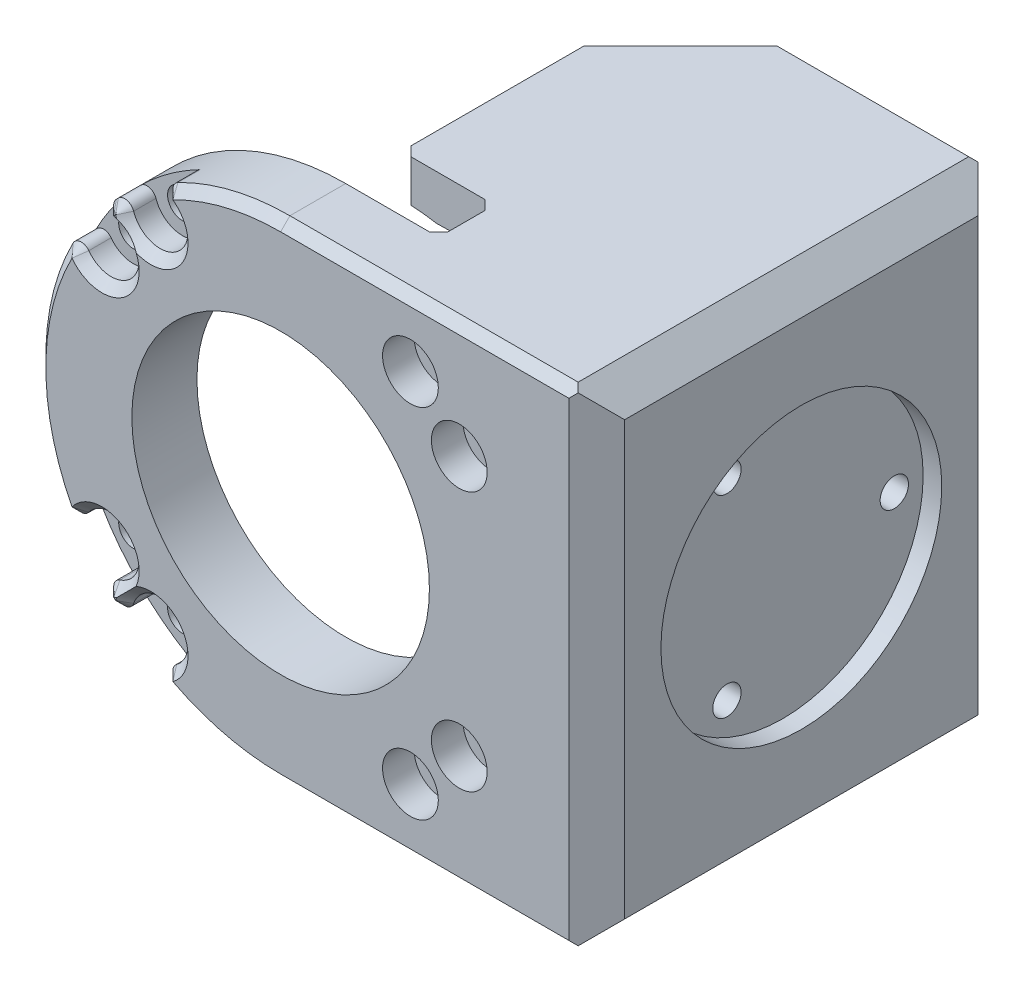
SolidWorks part; units mm, degrees
other "标注1"
sketch "草图23" plane through (38, 52.5005, -37) normal (0.8245, 0.2959, -0.4823) x (-0.5412, 0.1636, -0.8248)
material "ABS"
ref_plane "前视基准面" through (0, 0, 0) normal (0, 0, 1) x (1, 0, 0)
ref_plane "上视基准面" through (0, 0, 0) normal (0, 1, 0) x (1, 0, 0)
ref_plane "右视基准面" through (0, 0, 0) normal (1, 0, 0) x (0, 0, -1)
other "Configuration Table"
sketch "草图1" plane through (0, 0, 0) normal (0, 0, 1) x (1, 0, 0)
  line L2 (0, 0) -> (0, 52.5) construction
  line L6 (-26.25, 26.25) -> (30, 26.25) construction
  line L7 (0, 26.25) -> (-13.9599, 7.0358) construction
  line L8 (0, 26.25) -> (-19.2142, 12.2901) construction
  line L23 (0, 0) -> (30, 0)
  line L24 (0, 0) -> (0, 52.5) construction
  line L25 (0, 52.5) -> (30, 52.5)
  line L26 (30, 0) -> (30, 52.5)
  circle A2 centre (0, 26.25) radius 16
  circle A4 centre (0, 26.25) radius 23.75 construction
  arc A25 (0, 52.5) -> (0, 0) centre (0, 26.25) ccw
  dimension "D3" = 32
  dimension "D6" = 47.5
  dimension "D1" = 52.5
  dimension "D2" = 30
  dimension "D9" = 36
  dimension "D10" = 36
extrude "凸台-拉伸1" add sketch "草图1" along normal blind 7
sketch "草图2" plane through (30, 0, 0) normal (1, 0, 0) x (0, 0, -1)
  line L0 (-7, 52.5) -> (0, 52.5) construction
  line L1 (-7, 0) -> (37, 0)
  line L2 (-7, 0) -> (-7, 52.5)
  line L3 (-7, 52.5) -> (37, 52.5)
  line L4 (37, 0) -> (37, 52.5)
  dimension "D1" = 44
extrude "凸台-拉伸2" add sketch "草图2" along normal blind 4
chamfer "倒角1" distance 3 angle 45 2 edges at (34, 26.25, -37) (34, 26.25, 7)
sketch "草图6" plane through (34, 0, 0) normal (1, 0, 0) x (0, 0, -1)
  line L0 (-4, 0) -> (34, 0) construction
  line L3 (-7, 0) -> (-7, 52.5) construction
  circle A1 centre (15, 26.25) radius 12 construction
  circle A2 centre (27, 26.25) radius 1.525
  circle A3 centre (9, 15.8577) radius 1.525
  circle A4 centre (9, 36.6423) radius 1.525
  dimension "D4" = 24
  dimension "D5" = 3.05
  dimension "D1" = 26.25
  dimension "D2" = 22
  dimension "D6" = 3
sketch "草图16" plane through (0, 0, 0) normal (0, 0, -1) x (-1, 0, 0)
  line L2 (-30, 52.5) -> (0, 52.5)
  line L3 (0, 52.5) -> (0, 48)
  line L4 (-30, 0) -> (0, 0)
  line L5 (-30, 52.5) -> (-30, 0)
  line L6 (-21.4196, 30.0268) -> (0, 26.25) construction
  line L7 (0, 26.25) -> (-21.4196, 22.4732) construction
  line L8 (0, 26.25) -> (-30, 26.25) construction
  line L9 (0, 26.25) -> (0, 52.5) construction
  line L10 (0, 26.25) -> (0, 0) construction
  line L11 (0, 26.25) -> (-3.7768, 47.6696) construction
  line L12 (0, 26.25) -> (-3.7768, 4.8304) construction
  line L13 (0, 4.5) -> (0, 0)
  line L14 (-13.2899, 47.8727) -> (-3.7768, 47.6696)
  line L16 (-21.6834, 39.8188) -> (-21.4196, 30.0268)
  line L18 (-21.4196, 22.4732) -> (-21.6227, 12.9601)
  line L19 (-13.5688, 4.5666) -> (-3.7768, 4.8304)
  line L20 (-13.9599, 45.4642) -> (0, 26.25) construction
  line L21 (0, 26.25) -> (-13.9599, 7.0358) construction
  line L22 (-19.2142, 40.2099) -> (0, 26.25) construction
  line L23 (-19.2142, 12.2901) -> (0, 26.25) construction
  circle A0 centre (0, 26.25) radius 26.25 construction
  circle A1 centre (0, 26.25) radius 21.75 construction
  circle A2 centre (0, 26.25) radius 16 construction
  circle A3 centre (-13.9599, 45.4642) radius 2.5 construction
  circle A4 centre (-19.2142, 40.2099) radius 2.5 construction
  circle A5 centre (-19.2142, 12.2901) radius 2.5 construction
  circle A6 centre (-13.9599, 7.0358) radius 2.5 construction
  arc A8 (-21.4196, 30.0268) -> (-21.4196, 22.4732) centre (0, 26.25) ccw
  arc A11 (-15.4294, 47.4867) -> (-21.2367, 41.6794) centre (0, 26.25) ccw
  arc A12 (-3.7768, 47.6696) -> (0, 48) centre (0, 26.25) cw
  arc A13 (-3.7768, 4.8304) -> (0, 4.5) centre (0, 26.25) ccw
  arc A14 (-21.2367, 10.8206) -> (-15.4294, 5.0133) centre (0, 26.25) ccw
  arc A15 (-15.4294, 47.4867) -> (-13.2899, 47.8727) centre (-13.9599, 45.4642) cw
  arc A16 (-21.2367, 41.6794) -> (-21.6834, 39.8188) centre (-19.2142, 40.2099) ccw
  arc A17 (-21.2367, 10.8206) -> (-21.6227, 12.9601) centre (-19.2142, 12.2901) cw
  arc A18 (-15.4294, 5.0133) -> (-13.5688, 4.5666) centre (-13.9599, 7.0358) ccw
  circle A19 centre (0, 26.25) radius 23.75 construction
  point P9 (0, 0)
  dimension "D1" = 52.5
  dimension "D2" = 43.5
  dimension "D5" = 10
  dimension "D3" = 10
  dimension "D8" = 47.5
  dimension "D12" = 5
  dimension "D13" = 5
  dimension "D4" = 10
  dimension "D6" = 10
  dimension "D7" = 36
  dimension "D9" = 36
  dimension "D10" = 36
  dimension "D11" = 36
extrude "凸台-拉伸5" add sketch "草图16" along normal blind 37
chamfer "倒角7" distance 10 angle 45 2 edges at (0, 2.25, -37) (0, 50.25, -37)
chamfer "倒角8" distance 3 angle 45 2 edges at (34, 0, -15) (34, 52.5, -15)
chamfer "倒角9" distance 1 angle 45 5 edges at (5, 52.5, -32) (20.5, 52.5, -37) (20.5, 0, -37) (5, 0, -32) (0, 0, -13.5)
sketch "草图18" plane through (0, 0, 7) normal (0, 0, 1) x (1, 0, 0)
  line L0 (0, 26.25) -> (0, 2.5) construction
  line L1 (0, 26.25) -> (-23.75, 26.25) construction
  line L2 (0, 26.25) -> (-19.2142, 12.2901) construction
  line L3 (0, 26.25) -> (-13.9599, 7.0358) construction
  circle A0 centre (0, 26.25) radius 23.75 construction
  point P3 (-19.2142, 12.2901)
  point P6 (-13.9599, 7.0358)
  point P12 (-13.9599, 45.4642)
  point P13 (-19.2142, 40.2099)
  point P14 (19.2142, 40.2099)
  point P15 (13.9599, 45.4642)
  point P16 (13.9599, 7.0358)
  point P17 (19.2142, 12.2901)
  dimension "D1" = 47.5
  dimension "D2" = 36
  dimension "D3" = 36
  dimension "D4" = 4
hole_wizard "M3 六角圆柱头螺钉的柱形沉头孔1" positions "草图18" profile "草图19" counterbore size "M3" standard "GB" end condition through all
sketch "草图19" plane through (19.2142, 12.2901, 7) normal (1, 0, 0) x (0, -1, 0)
  line L0 (0, 0) -> (0, 44)
  line L1 (0, 44) -> (1.6, 44)
  line L3 (1.6, 44) -> (1.6, 3.4)
  line L4 (1.6, 3.4) -> (3, 3.4)
  line L5 (3, 3.4) -> (3, 0)
  line L7 (3, 0) -> (0, 0)
  line L11 (0, -6.35) -> (0, 107.95) construction
  dimension "通孔孔直径" = 3.2
  dimension "通孔孔深度" = 44
  dimension "柱形沉头孔直径" = 6
  dimension "柱形沉头孔深度" = 3.4
fillet "圆角11" radius 1 8 edges at (-13.9857, 4.036, 5.3) (-16.805, 6.0843, 5.3) (-20.1657, 9.445, 5.3) (-22.214, 12.2643, 5.3) (-22.214, 40.2357, 5.3) (-20.1657, 43.055, 5.3) (-16.805, 46.4157, 5.3) (-13.9857, 48.464, 5.3)
chamfer "倒角11" distance 1 angle 45 19 edges at (15.5, 52.5, 7) (-6.1983, 51.7577, 7) (-12.584, 48.7634, 7) (-12.1965, 43.0371, 7) (-17.5229, 45.1751, 7) (-18.5616, 44.8116, 7) (-18.9251, 43.7729, 7) (-16.7871, 38.4465, 7) (-22.5134, 38.834, 7) (-26.25, 26.25, 7) (-22.5134, 13.666, 7) (-16.7871, 14.0535, 7) (-18.9251, 8.7271, 7) (-18.5616, 7.6884, 7) (-17.5229, 7.3249, 7) (-12.1965, 9.4629, 7) (-12.584, 3.7366, 7) (-6.1983, 0.7423, 7) (15.5, 0, 7)
sketch "草图24" plane through (0, 0, 0) normal (-1, 0, 0) x (0, 0, 1)
  line L0 (-25.5858, 52.5) -> (0, 52.5) construction
  line L1 (-6, 52.5) -> (0, 52.5)
  line L2 (-6, 52.5) -> (-6, 0)
  line L3 (-6, 0) -> (0, 0)
  line L4 (0, 52.5) -> (0, 0)
  dimension "D1" = 6
extrude "切除-拉伸3" cut sketch "草图24" against normal blind 10
chamfer "倒角12" distance 1 angle 45 6 edges at (10, 2.3314, 0) (10, 2.3314, -6) (0, 2.75, -6) (0, 50.25, -6) (10, 50.1512, -6) (10, 50.1512, 0)
extrude "切除-拉伸4" cut sketch "草图6" against normal through all
sketch "草图25" plane through (34, 0, 0) normal (1, 0, 0) x (0, 0, -1)
  line L0 (-7, 1) -> (-7, 51.5) construction
  line L4 (36, 0) -> (-6, 0) construction
  circle A0 centre (15, 26.25) radius 15.1
  dimension "D1" = 22
  dimension "D2" = 30.2
  dimension "D3" = 26.25
extrude "切除-拉伸5" cut sketch "草图25" against normal blind 2
